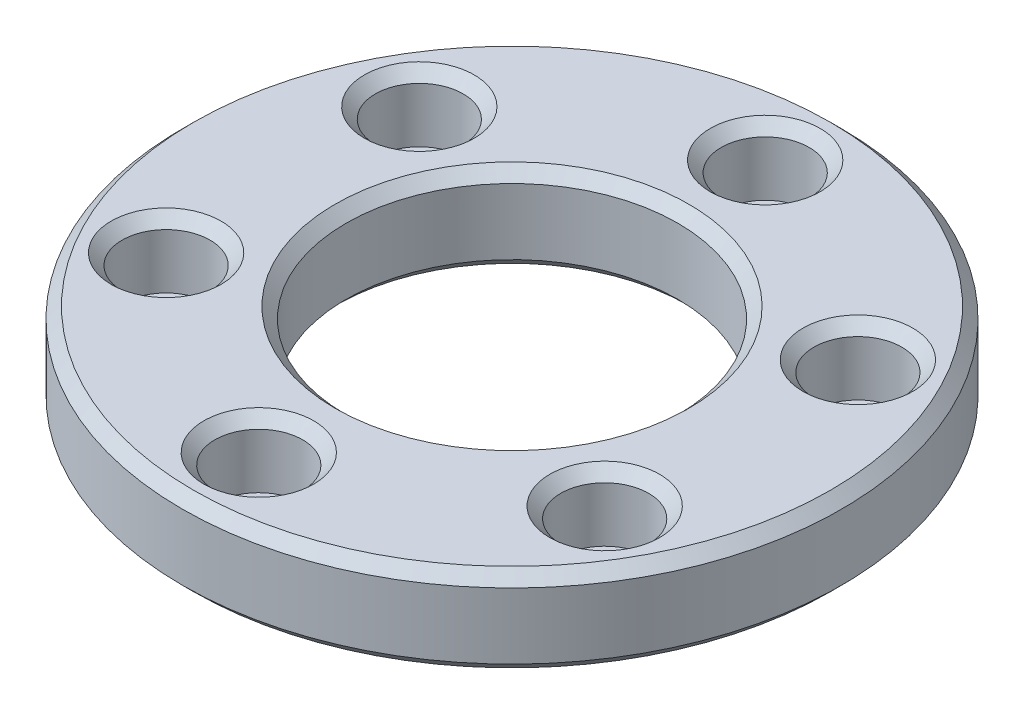
SolidWorks part; units mm, degrees
ref_plane "前视基准面" through (0, 0, 0) normal (0, 0, 1) x (1, 0, 0)
ref_plane "上视基准面" through (0, 0, 0) normal (0, 1, 0) x (1, 0, 0)
ref_plane "右视基准面" through (0, 0, 0) normal (1, 0, 0) x (0, 0, -1)
other "Configuration Table"
sketch "草图1" plane through (0, 0, 0) normal (0, 1, 0) x (1, 0, 0)
  circle A0 centre (0, 0) radius 7.55
  circle A1 centre (0, 0) radius 15
  circle A2 centre (0, 0) radius 11.525 construction
  circle A3 centre (0, 11.525) radius 2
  circle A4 centre (9.9809, 5.7625) radius 2
  circle A5 centre (9.9809, -5.7625) radius 2
  circle A6 centre (0, -11.525) radius 2
  circle A7 centre (-9.9809, -5.7625) radius 2
  circle A8 centre (-9.9809, 5.7625) radius 2
  point P19 (0, 0)
  dimension "D1" = 15.1
  dimension "D2" = 30
  dimension "D3" = 23.05
  dimension "D4" = 4
  dimension "D5" = 6
extrude "凸台-拉伸1" add sketch "草图1" along normal blind 3
sketch "草图2" plane through (0, 0, 0) normal (0, -1, 0) x (-1, 0, 0)
  circle A0 centre (0, 0) radius 7.55 construction
  circle A1 centre (0, 0) radius 15 construction
  circle A2 centre (0, 0) radius 7.55
  circle A3 centre (0, 0) radius 15
extrude "凸台-拉伸2" add sketch "草图2" along normal blind 1
chamfer "倒角1" distance 0.5 angle 45 10 edges at (0, -1, -7.55) (0, -1, -15) (-9.9809, 3, -3.7625) (0, 3, 13.525) (9.9809, 3, -3.7625) (0, 3, 7.55) (0, 3, 15) (0, 3, -9.525) (9.9809, 3, 7.7625) (-9.9809, 3, 7.7625)
